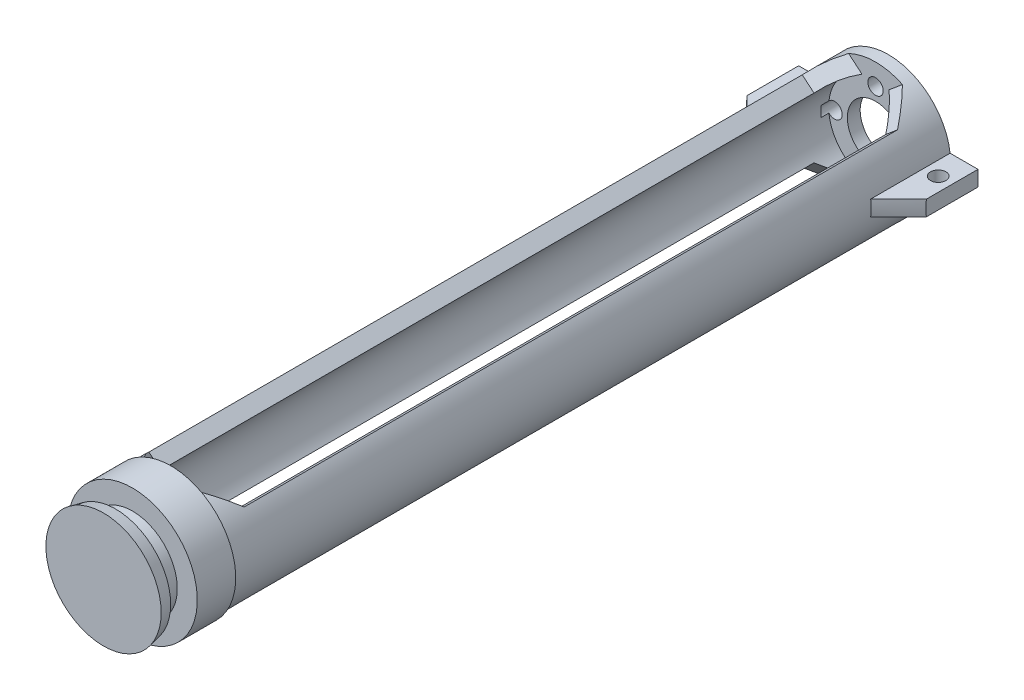
SolidWorks part; units mm, degrees
ref_plane "Front Plane" through (0, 0, 0) normal (0, 0, 1) x (1, 0, 0)
ref_plane "Top Plane" through (0, 0, 0) normal (0, 1, 0) x (1, 0, 0)
ref_plane "Right Plane" through (0, 0, 0) normal (1, 0, 0) x (0, 0, -1)
sketch "Sketch1" plane through (0, 0, 0) normal (0, 0, 1) x (1, 0, 0)
  circle A0 centre (0, 0) radius 11.25
  dimension "D1" = 22.5
ref_plane "Plane1" through (0, 0, -2.35) normal (0, 0, 1) x (1, 0, 0)
sketch "Sketch3" plane through (0, 0, -2.35) normal (0, 0, 1) x (1, 0, 0)
  circle A0 centre (0, 0) radius 10.75
  dimension "D1" = 21.5
loft "Loft1" add profiles "Sketch1", "Sketch3"
sketch "Sketch4" plane through (0, 0, -2.35) normal (0, 0, -1) x (-1, 0, 0)
  circle A0 centre (0, 0) radius 8.75
  dimension "D1" = 17.5
extrude "Boss-Extrude1" add sketch "Sketch4" along normal blind 3.3
sketch "Sketch5" plane through (0, 0, -5.65) normal (0, 0, -1) x (-1, 0, 0)
  circle A0 centre (0, 0) radius 12.65
  dimension "D1" = 25.3
extrude "Boss-Extrude2" add sketch "Sketch5" along normal blind 7.5
sketch "Sketch6" plane through (0, 0, -13.15) normal (0, 0, -1) x (-1, 0, 0)
  line L3 (0, 0) -> (0, 12.65) construction
  line L7 (-9.2951, -7.8246) -> (-7, -5.8926)
  line L8 (9.2951, -7.8246) -> (7, -5.8926)
  line L9 (0, 0) -> (12.15, 0) construction
  line L10 (-9.2951, 7.8246) -> (-7, 5.8926)
  line L11 (9.2951, 7.8246) -> (7, 5.8926)
  arc A0 (-9.2951, -7.8246) -> (-9.2951, 7.8246) centre (0, 0) cw
  arc A1 (-7, -5.8926) -> (-7, 5.8926) centre (0, 0) cw
  circle A2 centre (0, 0) radius 12.65 construction
  arc A3 (-9.2951, -7.8246) -> (9.2951, -7.8246) centre (0, 0) cw construction
  arc A4 (9.2951, 7.8246) -> (9.2951, -7.8246) centre (0, 0) cw
  arc A5 (7, 5.8926) -> (7, -5.8926) centre (0, 0) cw
  arc A6 (-7, -5.8926) -> (7, -5.8926) centre (0, 0) cw construction
  point P10 (0, 12.65)
  dimension "D2" = 0.5
  dimension "D3" = 14
  dimension "D1" = 3
extrude "Boss-Extrude3" add sketch "Sketch6" along normal blind 137.5
ref_plane "Plane2" through (0, 0, -150.65) normal (0, 0, 1) x (1, 0, 0)
sketch "Sketch7" plane through (0, 0, -150.65) normal (0, 0, 1) x (1, 0, 0)
  circle A0 centre (0, 0) radius 12.15
extrude "Boss-Extrude4" add sketch "Sketch7" against normal blind 2.5
sketch "Sketch8" plane through (0, 0, -153.15) normal (0, 0, -1) x (-1, 0, 0)
  circle A0 centre (0, 0) radius 5.5
  circle A1 centre (0, 0) radius 8 construction
  point P15 (0, 0)
  dimension "D1" = 11
  dimension "D2" = 16
extrude "Cut-Extrude1" cut sketch "Sketch8" against normal blind 3
sketch "Sketch9" plane through (0, 0, -153.15) normal (0, 0, -1) x (-1, 0, 0)
  circle A0 centre (0, 0) radius 8 construction
  circle A1 centre (0, 8) radius 1.5
  circle A2 centre (8, 0) radius 1.5
  circle A3 centre (0, -8) radius 1.5
  circle A4 centre (-8, 0) radius 1.5
  point P5 (0, 0)
  point P6 (0, 0)
  point P14 (0, 0)
  dimension "D1" = 16
  dimension "D2" = 3
  dimension "D3" = 4
extrude "Cut-Extrude2" cut sketch "Sketch9" against normal blind 4
chamfer "Chamfer3" distance 0.5 angle 45 1 edges at (-12.15, 0, -13.15)
sketch "Sketch10" plane through (0, 0, -13.15) normal (0, 0, -1) x (-1, 0, 0)
  circle A0 centre (0, 0) radius 9.15
extrude "Cut-Extrude3" cut sketch "Sketch10" against normal blind 5
chamfer "Chamfer4" distance 5 angle 45 1 edges at (-9.15, 0, -8.15)
chamfer "Chamfer5" distance 5 angle 45 4 edges at (8.1475, -6.8586, -13.15) (-8.3388, -7.0196, -13.15) (8.1475, 6.8586, -13.15) (-8.3388, 7.0196, -13.15)
sketch "Sketch11" plane through (0, 0, 0) normal (0, 1, 0) x (1, 0, 0)
  line L0 (0, 153.15) -> (0, 129.5805) construction
  line L1 (12.15, 153.15) -> (-12.15, 153.15) construction
  line L2 (-18.5, 200.6094) -> (-18.5, 18.1094) construction
  line L3 (-11.15, 153.15) -> (-17.5, 153.15)
  line L4 (-11.15, 153.15) -> (-11.15, 143.15)
  line L5 (-11.15, 143.15) -> (-17.5, 143.15)
  line L6 (-17.5, 153.15) -> (-17.5, 143.15)
  line L7 (11.15, 143.15) -> (17.5, 143.15)
  line L8 (17.5, 153.15) -> (17.5, 143.15)
  line L9 (11.15, 153.15) -> (17.5, 153.15)
  line L10 (11.15, 153.15) -> (11.15, 143.15)
  line L11 (-11.15, 148.15) -> (-12.15, 148.15) construction
  line L12 (-12.15, 153.15) -> (-12.15, 13.65) construction
  dimension "D1" = 1
  dimension "D2" = 10
  dimension "D3" = 1
extrude "Boss-Extrude5" add sketch "Sketch11" along normal mid plane 3
ref_plane "Plane3" through (0, 0, -81.9) normal (0, 0, -1) x (-1, 0, 0)
chamfer "Chamfer6" distance 5 angle 45 4 edges at (-8.1475, -6.8586, -150.65) (8.1475, -6.8586, -150.65) (-8.1475, 6.8586, -150.65) (8.1475, 6.8586, -150.65)
chamfer "Chamfer7" distance 5.5 angle 45 2 edges at (12.15, 0, -143.15) (-12.15, 0, -143.15)
sketch "Sketch12" plane through (0, 1.5, 0) normal (0, 1, 0) x (1, 0, 0)
  line L0 (17.5, 148.1071) -> (12.0571, 148.1071) construction
  line L1 (17.5, 143.0642) -> (17.5, 153.15) construction
  line L2 (12.0571, 137.65) -> (12.0571, 153.15) construction
  circle A0 centre (14.7785, 148.1071) radius 1.5
  dimension "D1" = 3
extrude "Cut-Extrude4" cut sketch "Sketch12" against normal blind 10
